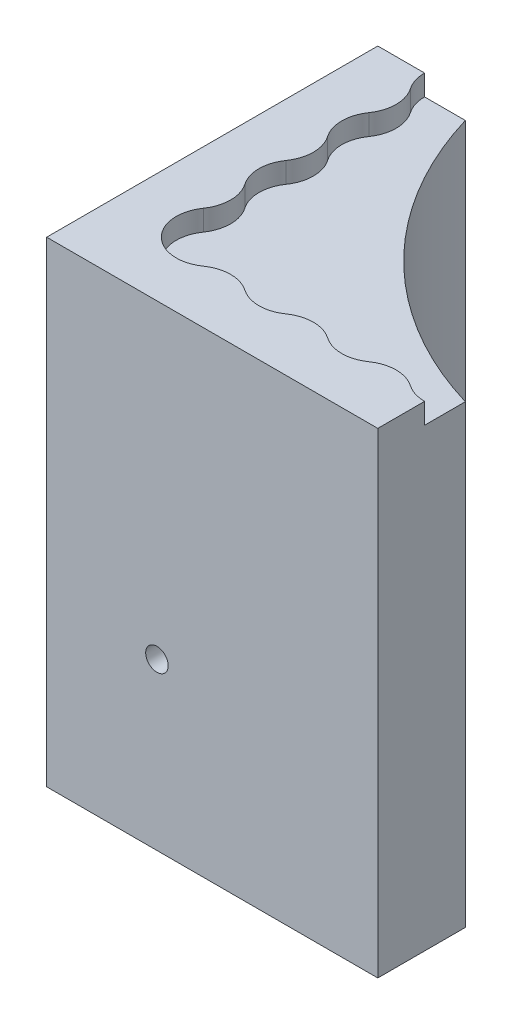
SolidWorks part; units mm, degrees
material "PET"
ref_plane "Front" through (0, 0, 0) normal (0, 0, 1) x (1, 0, 0)
ref_plane "Top" through (0, 0, 0) normal (0, 1, 0) x (1, 0, 0)
ref_plane "Right" through (0, 0, 0) normal (1, 0, 0) x (0, 0, -1)
sketch "Sketch1" plane through (0, 0, 0) normal (0, 1, 0) x (1, 0, 0)
  line L1 (0, 0) -> (50.8, 0)
  line L2 (0, 0) -> (0, 50.8)
  line L3 (0, 50.8) -> (50.8, 50.8)
  line L4 (50.8, 0) -> (50.8, 50.8)
  circle A0 centre (66.675, 66.675) radius 55.5625 construction
  dimension "D1" = 66.675
  dimension "D2" = 111.125
  dimension "D3" = 66.675
  dimension "D4" = 50.8
extrude "Boss-Extrude1" add sketch "Sketch1" along normal blind 73.025
sketch "Sketch2" plane through (0, 73.025, 0) normal (0, 1, 0) x (1, 0, 0)
  line L8 (129.2582, 124.9484) -> (133.499, 78.5045) construction
  line L9 (85.192, 137.4546) -> (125.4736, 129.1805) construction
  line L10 (129.2582, 124.9484) -> (133.499, 78.5045) construction
  line L11 (85.192, 137.4546) -> (125.4736, 129.1805) construction
  line L12 (130.017, 125.0177) -> (134.2578, 78.5738)
  line L13 (85.3453, 138.201) -> (125.6269, 129.9269)
  arc A0 (8.7916, 91.6214) -> (8.7916, 98.8786) centre (3.5805, 95.25) ccw construction
  arc A1 (8.7916, 91.6214) -> (8.7916, 86.1786) centre (12.7, 88.9) ccw construction
  arc A2 (8.7916, 78.9214) -> (8.7916, 86.1786) centre (3.5805, 82.55) ccw construction
  arc A3 (8.7916, 78.9214) -> (8.7796, 73.4959) centre (12.7, 76.2) ccw construction
  arc A4 (8.8014, 66.3169) -> (8.7796, 73.4959) centre (3.5524, 69.8905) ccw construction
  arc A5 (8.8014, 66.3169) -> (8.8053, 60.7032) centre (12.9199, 63.5129) ccw construction
  arc A6 (8.7834, 53.5096) -> (8.8053, 60.7032) centre (3.5613, 57.1223) ccw construction
  arc A7 (8.7834, 53.5096) -> (8.7916, 48.0786) centre (12.7, 50.8) ccw construction
  arc A8 (8.7916, 40.8214) -> (8.7916, 48.0786) centre (3.5805, 44.45) ccw construction
  arc A9 (8.7916, 40.8214) -> (8.7916, 35.3786) centre (12.7, 38.1) ccw construction
  arc A10 (8.7916, 28.1214) -> (8.7916, 35.3786) centre (3.5805, 31.75) ccw construction
  arc A11 (8.7916, 28.1214) -> (8.7916, 22.6786) centre (12.7, 25.4) ccw construction
  arc A12 (8.7916, 15.4214) -> (8.7916, 22.6786) centre (3.5805, 19.05) ccw construction
  arc A13 (8.7916, 15.4214) -> (15.4214, 8.7916) centre (12.7, 12.7) ccw construction
  arc A14 (22.6786, 8.7916) -> (15.4214, 8.7916) centre (19.05, 3.5805) ccw construction
  arc A15 (22.6786, 8.7916) -> (28.1214, 8.7916) centre (25.4, 12.7) ccw construction
  arc A16 (35.3786, 8.7916) -> (28.1214, 8.7916) centre (31.75, 3.5805) ccw construction
  arc A17 (35.3786, 8.7916) -> (40.8214, 8.7916) centre (38.1, 12.7) ccw construction
  arc A18 (48.0786, 8.7916) -> (40.8214, 8.7916) centre (44.45, 3.5805) ccw construction
  arc A19 (48.0786, 8.7916) -> (53.5096, 8.7834) centre (50.8, 12.7) ccw construction
  arc A20 (60.7032, 8.8053) -> (53.5096, 8.7834) centre (57.1223, 3.5613) ccw construction
  arc A21 (60.7032, 8.8053) -> (66.3169, 8.8014) centre (63.5129, 12.9199) ccw construction
  arc A22 (73.4959, 8.7796) -> (66.3169, 8.8014) centre (69.8905, 3.5524) ccw construction
  arc A23 (73.4959, 8.7796) -> (78.9214, 8.7916) centre (76.2, 12.7) ccw construction
  arc A24 (86.1786, 8.7916) -> (78.9214, 8.7916) centre (82.55, 3.5805) ccw construction
  arc A25 (86.1786, 8.7916) -> (91.6214, 8.7916) centre (88.9, 12.7) ccw construction
  arc A26 (98.8786, 8.7916) -> (91.6214, 8.7916) centre (95.25, 3.5805) ccw construction
  arc A27 (98.8786, 8.7916) -> (105.5642, 15.3394) centre (101.6, 12.7) ccw construction
  arc A28 (113.5841, 27.9306) -> (105.5642, 15.3394) centre (112.3572, 19.8624) ccw construction
  arc A29 (113.5841, 27.9306) -> (119.0625, 32.6538) centre (114.3, 32.639) ccw construction
  arc A30 (119.9168, 35.8549) -> (119.0625, 32.6538) centre (125.4124, 32.6736) ccw construction
  arc A31 (119.9168, 35.8549) -> (127.8227, 59.9277) centre (66.675, 66.675) ccw construction
  arc A32 (132.1466, 72.652) -> (127.8227, 59.9277) centre (158.75, 56.515) ccw construction
  arc A33 (132.1466, 72.652) -> (133.499, 78.5045) centre (123.9376, 77.6314) ccw construction
  arc A34 (129.2582, 124.9484) -> (125.4736, 129.1805) centre (124.5154, 124.5154) ccw construction
  arc A35 (85.192, 137.4546) -> (76.9535, 135.2891) centre (83.2602, 128.0498) ccw construction
  arc A36 (59.9277, 127.8227) -> (76.9535, 135.2891) centre (56.515, 158.75) ccw construction
  arc A37 (59.9277, 127.8227) -> (35.8549, 119.9168) centre (66.675, 66.675) ccw construction
  arc A38 (32.6538, 119.0625) -> (35.8549, 119.9168) centre (32.6736, 125.4124) ccw construction
  arc A39 (32.6538, 119.0625) -> (27.9306, 113.5841) centre (32.639, 114.3) ccw construction
  arc A40 (15.3394, 105.5642) -> (27.9306, 113.5841) centre (19.8624, 112.3572) ccw construction
  arc A41 (15.3394, 105.5642) -> (8.7916, 98.8786) centre (12.7, 101.6) ccw construction
  arc A42 (8.7916, 91.6214) -> (8.7916, 98.8786) centre (3.5805, 95.25) ccw construction
  arc A43 (8.7916, 91.6214) -> (8.7916, 86.1786) centre (12.7, 88.9) ccw construction
  arc A44 (8.7916, 78.9214) -> (8.7916, 86.1786) centre (3.5805, 82.55) ccw construction
  arc A45 (8.7916, 78.9214) -> (8.7796, 73.4959) centre (12.7, 76.2) ccw construction
  arc A46 (8.8014, 66.3169) -> (8.7796, 73.4959) centre (3.5524, 69.8905) ccw construction
  arc A47 (8.8014, 66.3169) -> (8.8053, 60.7032) centre (12.9199, 63.5129) ccw construction
  arc A48 (8.7834, 53.5096) -> (8.8053, 60.7032) centre (3.5613, 57.1223) ccw construction
  arc A49 (8.7834, 53.5096) -> (8.7916, 48.0786) centre (12.7, 50.8) ccw construction
  arc A50 (8.7916, 40.8214) -> (8.7916, 48.0786) centre (3.5805, 44.45) ccw construction
  arc A51 (8.7916, 40.8214) -> (8.7916, 35.3786) centre (12.7, 38.1) ccw construction
  arc A52 (8.7916, 28.1214) -> (8.7916, 35.3786) centre (3.5805, 31.75) ccw construction
  arc A53 (8.7916, 28.1214) -> (8.7916, 22.6786) centre (12.7, 25.4) ccw construction
  arc A54 (8.7916, 15.4214) -> (8.7916, 22.6786) centre (3.5805, 19.05) ccw construction
  arc A55 (8.7916, 15.4214) -> (15.4214, 8.7916) centre (12.7, 12.7) ccw construction
  arc A56 (22.6786, 8.7916) -> (15.4214, 8.7916) centre (19.05, 3.5805) ccw construction
  arc A57 (22.6786, 8.7916) -> (28.1214, 8.7916) centre (25.4, 12.7) ccw construction
  arc A58 (35.3786, 8.7916) -> (28.1214, 8.7916) centre (31.75, 3.5805) ccw construction
  arc A59 (35.3786, 8.7916) -> (40.8214, 8.7916) centre (38.1, 12.7) ccw construction
  arc A60 (48.0786, 8.7916) -> (40.8214, 8.7916) centre (44.45, 3.5805) ccw construction
  arc A61 (48.0786, 8.7916) -> (53.5096, 8.7834) centre (50.8, 12.7) ccw construction
  arc A62 (60.7032, 8.8053) -> (53.5096, 8.7834) centre (57.1223, 3.5613) ccw construction
  arc A63 (60.7032, 8.8053) -> (66.3169, 8.8014) centre (63.5129, 12.9199) ccw construction
  arc A64 (73.4959, 8.7796) -> (66.3169, 8.8014) centre (69.8905, 3.5524) ccw construction
  arc A65 (73.4959, 8.7796) -> (78.9214, 8.7916) centre (76.2, 12.7) ccw construction
  arc A66 (86.1786, 8.7916) -> (78.9214, 8.7916) centre (82.55, 3.5805) ccw construction
  arc A67 (86.1786, 8.7916) -> (91.6214, 8.7916) centre (88.9, 12.7) ccw construction
  arc A68 (98.8786, 8.7916) -> (91.6214, 8.7916) centre (95.25, 3.5805) ccw construction
  arc A69 (98.8786, 8.7916) -> (105.5642, 15.3394) centre (101.6, 12.7) ccw construction
  arc A70 (113.5841, 27.9306) -> (105.5642, 15.3394) centre (112.3572, 19.8624) ccw construction
  arc A71 (113.5841, 27.9306) -> (119.0625, 32.6538) centre (114.3, 32.639) ccw construction
  arc A72 (119.9168, 35.8549) -> (119.0625, 32.6538) centre (125.4124, 32.6736) ccw construction
  arc A73 (119.9168, 35.8549) -> (127.8227, 59.9277) centre (66.675, 66.675) ccw construction
  arc A74 (132.1466, 72.652) -> (127.8227, 59.9277) centre (158.75, 56.515) ccw construction
  arc A75 (132.1466, 72.652) -> (133.499, 78.5045) centre (123.9376, 77.6314) ccw construction
  arc A76 (129.2582, 124.9484) -> (125.4736, 129.1805) centre (124.5154, 124.5154) ccw construction
  arc A77 (85.192, 137.4546) -> (76.9535, 135.2891) centre (83.2602, 128.0498) ccw construction
  arc A78 (59.9277, 127.8227) -> (76.9535, 135.2891) centre (56.515, 158.75) ccw construction
  arc A79 (59.9277, 127.8227) -> (35.8549, 119.9168) centre (66.675, 66.675) ccw construction
  arc A80 (32.6538, 119.0625) -> (35.8549, 119.9168) centre (32.6736, 125.4124) ccw construction
  arc A81 (32.6538, 119.0625) -> (27.9306, 113.5841) centre (32.639, 114.3) ccw construction
  arc A82 (15.3394, 105.5642) -> (27.9306, 113.5841) centre (19.8624, 112.3572) ccw construction
  arc A83 (15.3394, 105.5642) -> (8.7916, 98.8786) centre (12.7, 101.6) ccw construction
  arc A84 (132.7981, 72.2568) -> (134.2578, 78.5738) centre (123.9376, 77.6314) ccw
  arc A85 (132.7981, 72.2568) -> (128.5801, 59.8441) centre (158.75, 56.515) ccw
  arc A86 (120.5763, 35.4731) -> (128.5801, 59.8441) centre (66.675, 66.675) ccw
  arc A87 (120.5763, 35.4731) -> (119.8245, 32.6562) centre (125.4124, 32.6736) ccw
  arc A88 (113.4695, 27.1773) -> (119.8245, 32.6562) centre (114.3, 32.639) ccw
  arc A89 (113.4695, 27.1773) -> (106.1985, 15.7617) centre (112.3572, 19.8624) ccw
  arc A90 (98.4431, 8.1663) -> (106.1985, 15.7617) centre (101.6, 12.7) ccw
  arc A91 (98.4431, 8.1663) -> (92.0569, 8.1663) centre (95.25, 3.5805) ccw
  arc A92 (85.7431, 8.1663) -> (92.0569, 8.1663) centre (88.9, 12.7) ccw
  arc A93 (85.7431, 8.1663) -> (79.3569, 8.1663) centre (82.55, 3.5805) ccw
  arc A94 (73.0633, 8.1523) -> (79.3569, 8.1663) centre (76.2, 12.7) ccw
  arc A95 (73.0633, 8.1523) -> (66.7457, 8.1715) centre (69.8905, 3.5524) ccw
  arc A96 (60.2735, 8.176) -> (66.7457, 8.1715) centre (63.5129, 12.9199) ccw
  arc A97 (60.2735, 8.176) -> (53.9431, 8.1568) centre (57.1223, 3.5613) ccw
  arc A98 (47.6431, 8.1663) -> (53.9431, 8.1568) centre (50.8, 12.7) ccw
  arc A99 (47.6431, 8.1663) -> (41.2569, 8.1663) centre (44.45, 3.5805) ccw
  arc A100 (34.9431, 8.1663) -> (41.2569, 8.1663) centre (38.1, 12.7) ccw
  arc A101 (34.9431, 8.1663) -> (28.5569, 8.1663) centre (31.75, 3.5805) ccw
  arc A102 (22.2431, 8.1663) -> (28.5569, 8.1663) centre (25.4, 12.7) ccw
  arc A103 (22.2431, 8.1663) -> (15.8569, 8.1663) centre (19.05, 3.5805) ccw
  arc A104 (8.1663, 15.8569) -> (15.8569, 8.1663) centre (12.7, 12.7) ccw
  arc A105 (8.1663, 15.8569) -> (8.1663, 22.2431) centre (3.5805, 19.05) ccw
  arc A106 (8.1663, 28.5569) -> (8.1663, 22.2431) centre (12.7, 25.4) ccw
  arc A107 (8.1663, 28.5569) -> (8.1663, 34.9431) centre (3.5805, 31.75) ccw
  arc A108 (8.1663, 41.2569) -> (8.1663, 34.9431) centre (12.7, 38.1) ccw
  arc A109 (8.1663, 41.2569) -> (8.1663, 47.6431) centre (3.5805, 44.45) ccw
  arc A110 (8.1568, 53.9431) -> (8.1663, 47.6431) centre (12.7, 50.8) ccw
  arc A111 (8.1568, 53.9431) -> (8.176, 60.2735) centre (3.5613, 57.1223) ccw
  arc A112 (8.1715, 66.7457) -> (8.176, 60.2735) centre (12.9199, 63.5129) ccw
  arc A113 (8.1715, 66.7457) -> (8.1523, 73.0633) centre (3.5524, 69.8905) ccw
  arc A114 (8.1663, 79.3569) -> (8.1523, 73.0633) centre (12.7, 76.2) ccw
  arc A115 (8.1663, 79.3569) -> (8.1663, 85.7431) centre (3.5805, 82.55) ccw
  arc A116 (8.1663, 92.0569) -> (8.1663, 85.7431) centre (12.7, 88.9) ccw
  arc A117 (8.1663, 92.0569) -> (8.1663, 98.4431) centre (3.5805, 95.25) ccw
  arc A118 (15.7617, 106.1985) -> (8.1663, 98.4431) centre (12.7, 101.6) ccw
  arc A119 (15.7617, 106.1985) -> (27.1773, 113.4695) centre (19.8624, 112.3572) ccw
  arc A120 (32.6562, 119.8245) -> (27.1773, 113.4695) centre (32.639, 114.3) ccw
  arc A121 (32.6562, 119.8245) -> (35.4731, 120.5763) centre (32.6736, 125.4124) ccw
  arc A122 (59.8441, 128.5801) -> (35.4731, 120.5763) centre (66.675, 66.675) ccw
  arc A123 (59.8441, 128.5801) -> (76.4529, 135.8637) centre (56.515, 158.75) ccw
  arc A124 (85.3453, 138.201) -> (76.4529, 135.8637) centre (83.2602, 128.0498) ccw
  arc A125 (130.017, 125.0177) -> (125.6269, 129.9269) centre (124.5154, 124.5154) ccw
  dimension "D1" = 0.762
extrude "Cut-Extrude1" cut sketch "Sketch2" against normal blind 3.175
sketch "Sketch3" plane through (0, 73.025, 0) normal (0, 1, 0) x (1, 0, 0)
  circle A0 centre (66.675, 66.675) radius 55.5625 construction
  circle A1 centre (66.675, 66.675) radius 55.5625
extrude "Cut-Extrude2" cut sketch "Sketch3" against normal through all
hole_wizard "#8-32 Tapped Hole1" positions "Sketch4" profile "Sketch5" tap size "#8-32" standard "ANSI Inch"
sketch "Sketch4" plane through (393.7, -15.875, 0) normal (0, 0, 1) x (1, 0, 0)
  point P30 (-376.782, 41.275)
sketch "Sketch5" plane through (16.918, 25.4, 0) normal (1, 0, 0) x (0, -1, 0)
  line L0 (0, 0) -> (0, 11.7464)
  line L1 (0, 11.7464) -> (1.7272, 10.7086)
  line L2 (1.7272, 10.7086) -> (1.7272, 0)
  line L3 (1.7272, 0) -> (0, 0)
  line L4 (0, 11.7464) -> (-1.7272, 10.7086) construction
  line L5 (0, -6.35) -> (0, 107.95) construction
  dimension "Tap Drill Dia." = 3.4544
  dimension "Tap Drill Depth" = 10.7086
  dimension "Drill Angle" = 118
hole_wizard "#8-32 Tapped Hole2" positions "Sketch6" profile "Sketch7" tap size "#8-32" standard "ANSI Inch"
sketch "Sketch6" plane through (0, -15.875, -393.7) normal (-1, 0, 0) x (0, 0, 1)
  point P36 (374.968, 41.275)
sketch "Sketch7" plane through (0, 25.4, -18.732) normal (0, 1, 0) x (0, 0, 1)
  line L0 (0, 0) -> (0, 11.7464)
  line L1 (0, 11.7464) -> (1.7272, 10.7086)
  line L2 (1.7272, 10.7086) -> (1.7272, 0)
  line L3 (1.7272, 0) -> (0, 0)
  line L4 (0, 11.7464) -> (-1.7272, 10.7086) construction
  line L5 (0, -6.35) -> (0, 107.95) construction
  dimension "Tap Drill Dia." = 3.4544
  dimension "Tap Drill Depth" = 10.7086
  dimension "Drill Angle" = 118
